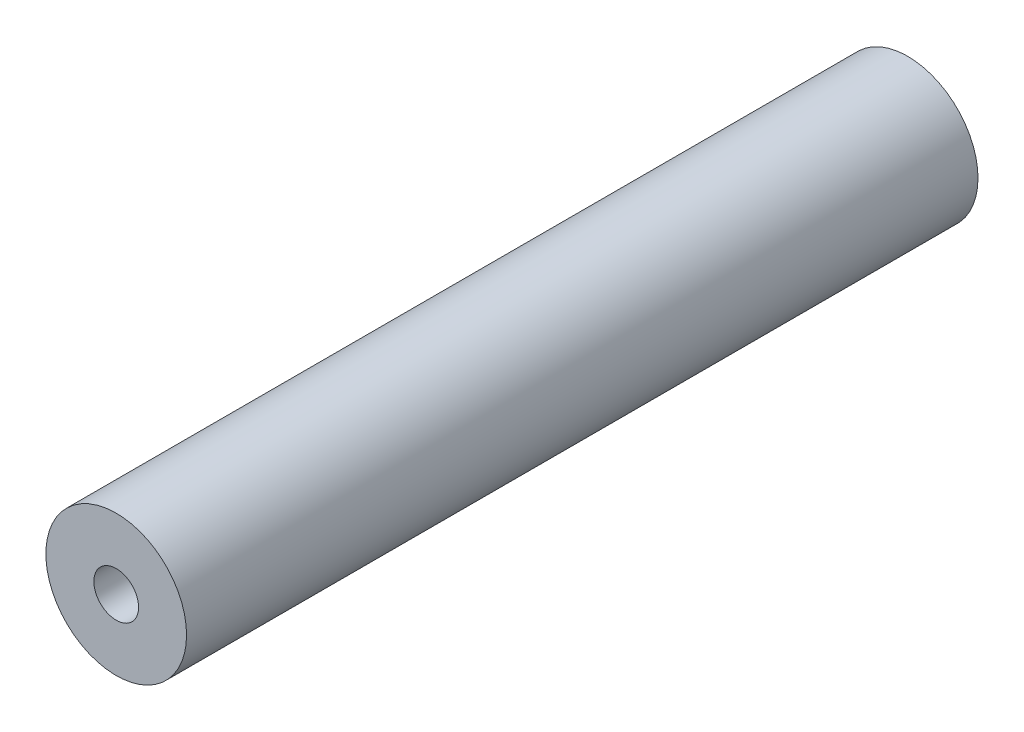
SolidWorks part; units mm, degrees
material "6061-T6 (SS)"
ref_plane "Front Plane" through (0, 0, 0) normal (0, 0, 1) x (1, 0, 0)
ref_plane "Top Plane" through (0, 0, 0) normal (0, 1, 0) x (1, 0, 0)
ref_plane "Right Plane" through (0, 0, 0) normal (1, 0, 0) x (0, 0, -1)
sketch "Sketch1" plane through (0, 0, 0) normal (0, 0, 1) x (1, 0, 0)
  circle A0 centre (0, 0) radius 6.35
  circle A1 centre (0, 0) radius 2.0193
  dimension "D1" = 4.0386
  dimension "D2" = 12.7
extrude "Boss-Extrude1" add sketch "Sketch1" along normal blind 71.4375
hole_wizard "#10-32 Tapped Hole1" positions "3DSketch1" profile "Sketch2" tap size "#10-32" standard "ANSI Inch" end condition through all
sketch3d "3DSketch1"
  line L0 (0, 0, 71.4375) -> (0, 0, 0) construction
  point P0 (0, 0, 71.4375)
  point P2 (0, 0, 0)
sketch "Sketch2" plane through (0, 0, 71.4375) normal (1, 0, 0) x (0, -1, 0)
  line L0 (0, 0) -> (0, 71.4375)
  line L1 (0, 71.4375) -> (2.0193, 71.4375)
  line L2 (2.0193, 71.4375) -> (2.0193, 0)
  line L5 (2.0193, 0) -> (0, 0)
  line L11 (0, -6.35) -> (0, 107.95) construction
  dimension "Thru Tap Drill Dia." = 4.0386
  dimension "Thru Tap Drill Depth" = 71.4375
cosmetic thread "Hole Thread1" parameters "D2"=4.826
cosmetic thread "Hole Thread2" parameters "D2"=4.826
